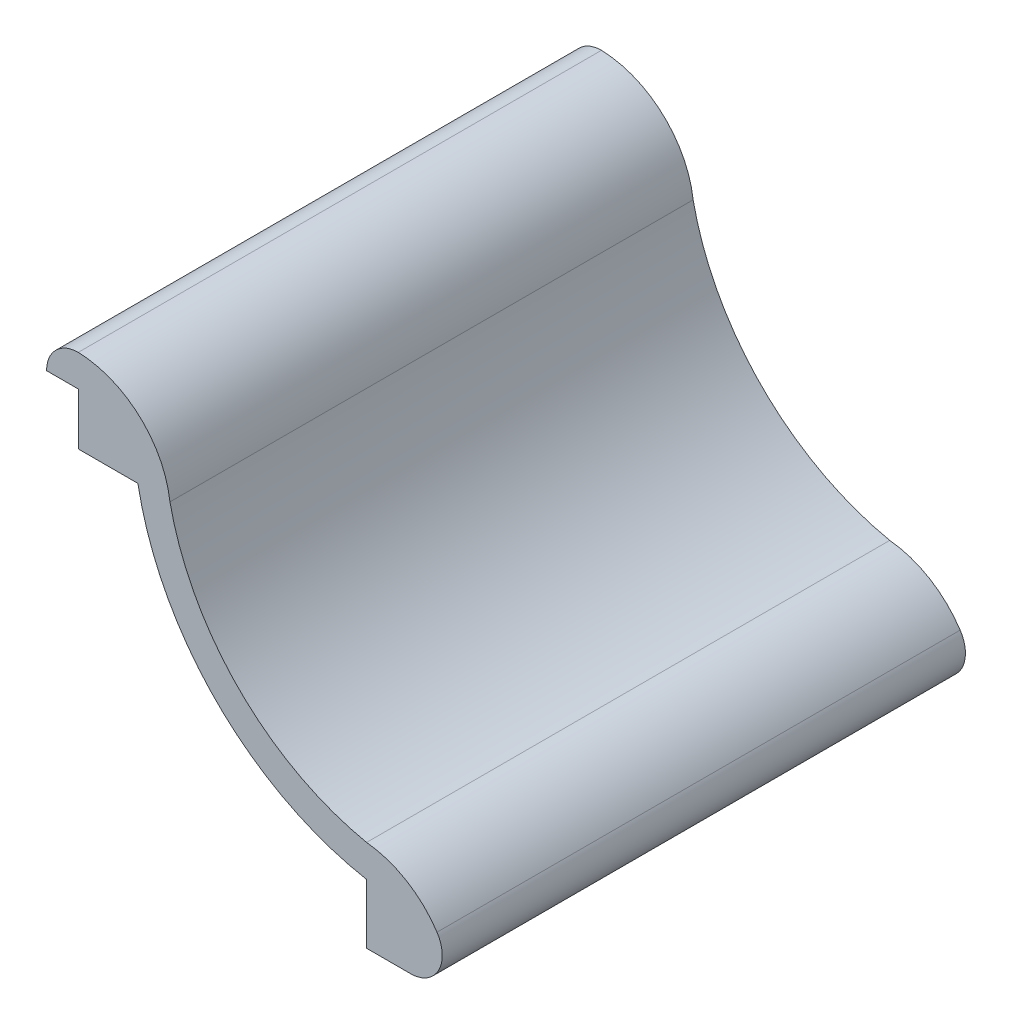
SolidWorks part; units mm, degrees
ref_plane "Front Plane" through (0, 0, 0) normal (0, 0, 1) x (1, 0, 0)
ref_plane "Top Plane" through (0, 0, 0) normal (0, 1, 0) x (1, 0, 0)
ref_plane "Right Plane" through (0, 0, 0) normal (1, 0, 0) x (0, 0, -1)
sketch "Sketch1" plane through (0, 0, 0) normal (0, 0, 1) x (1, 0, 0)
  line L4 (-45.7962, 45.7962) -> (0, 45.7962) construction
  line L6 (0, 45.7962) -> (0, 0) construction
  line L7 (-58.2422, 56.2102) -> (-58.2422, 62.5602)
  line L8 (10.922, -12.446) -> (17.272, -12.446)
  line L9 (-58.2422, 56.2102) -> (-58.2422, 45.7962) construction
  line L10 (-58.2422, 45.7962) -> (-45.7962, 45.7962) construction
  line L11 (0, 0) -> (0, -12.446) construction
  line L12 (0, -12.446) -> (10.922, -12.446) construction
  arc A6 (0, 0) -> (-45.7962, 45.7962) centre (10.3996, 56.1958) cw
  arc A7 (-45.7962, 45.7962) -> (-58.2422, 56.2102) centre (-58.3145, 43.4796) ccw
  arc A8 (0, 0) -> (10.922, -12.446) centre (-1.8079, -12.6018) cw
  arc A9 (-58.2422, 62.5602) -> (-39.3749, 45.7962) centre (-58.3145, 43.4796) cw
  arc A10 (-39.3749, 45.7962) -> (0, 6.4213) centre (10.3996, 56.1958) ccw
  arc A11 (0, 6.4213) -> (17.272, -12.446) centre (-1.8793, -12.6385) cw
  dimension "D1" = 45.7962
  dimension "D2" = 57.15
  dimension "D3" = 10.414
  dimension "D5" = 12.446
  dimension "D4" = 6.35
  dimension "D6" = 12.446
  dimension "D7" = 10.922
extrude "Boss-Extrude1" add sketch "Sketch1" along normal mid plane 209.55 contours L4 | A11 L8 A8 A6 A7 L7 A9 A10 region at (-42.5855, 44.9377, 0)
sketch "Sketch2" plane through (0, 0, 0) normal (0, 0, 1) x (1, 0, 0)
  line L0 (-58.2422, 56.2102) -> (-58.2422, 45.7962)
  line L1 (-58.2422, 45.7962) -> (-45.7962, 45.7962)
  line L2 (0, 0) -> (0, -12.446)
  line L3 (0, -12.446) -> (10.922, -12.446)
  arc A0 (-45.7962, 45.7962) -> (-58.2422, 56.2102) centre (-58.3145, 43.4796) ccw construction
  arc A1 (-45.7962, 45.7962) -> (0, 0) centre (10.3996, 56.1958) ccw construction
  arc A2 (-58.2422, 56.2102) -> (-45.7962, 45.7962) centre (-58.3145, 43.4796) cw
  arc A3 (0, 0) -> (10.922, -12.446) centre (-1.8079, -12.6018) cw
extrude "Boss-Extrude2" add sketch "Sketch2" along normal mid plane 185.1914
sketch "Sketch3" plane through (0, 0, -104.775) normal (0, 0, -1) x (-1, 0, 0)
  line L0 (58.2422, 56.2102) -> (58.2422, 45.7962)
  line L1 (58.2422, 45.7962) -> (45.7962, 45.7962)
  line L2 (0, 0) -> (0, -12.446)
  line L3 (0, -12.446) -> (-10.922, -12.446)
  arc A0 (-10.922, -12.446) -> (0, 0) centre (1.8079, -12.6018) cw
  arc A1 (45.7962, 45.7962) -> (58.2422, 56.2102) centre (58.3145, 43.4796) cw
extrude "Boss-Extrude3" add sketch "Sketch3" against normal offset from surface (5.8293 mm away) 6.35 up to face at (-53.4687, 50.0142, -92.5957)
sketch "Sketch4" plane through (0, 0, 104.775) normal (0, 0, 1) x (1, 0, 0)
  line L0 (-58.2422, 56.2102) -> (-58.2422, 45.7962)
  line L1 (-58.2422, 45.7962) -> (-45.7962, 45.7962)
  line L2 (0, 0) -> (0, -12.446)
  line L3 (0, -12.446) -> (10.922, -12.446)
  arc A0 (-58.2422, 56.2102) -> (-45.7962, 45.7962) centre (-58.3145, 43.4796) cw
  arc A1 (0, 0) -> (10.922, -12.446) centre (-1.8079, -12.6018) cw
extrude "Boss-Extrude4" add sketch "Sketch4" against normal blind 6.35
sketch "Sketch5" plane through (0, 0, 104.775) normal (0, 0, 1) x (1, 0, 0)
  line L0 (-58.2422, 45.7962) -> (-58.2422, 62.5602) construction
  line L2 (-57.7342, 44.7636) -> (-65.5217, 44.7636)
  line L3 (-57.7342, 44.7636) -> (-57.7342, 64.5974)
  line L4 (-57.7342, 64.5974) -> (-65.5217, 64.5974)
  line L5 (-65.5217, 44.7636) -> (-65.5217, 64.5974)
  line L6 (-3.152, -11.938) -> (19.6021, -11.938)
  line L7 (-3.152, -11.938) -> (-3.152, -15.345)
  line L8 (-3.152, -15.345) -> (19.6021, -15.345)
  line L9 (19.6021, -11.938) -> (19.6021, -15.345)
  line L10 (0, -12.446) -> (17.272, -12.446) construction
  dimension "D1" = 0.508
  dimension "D2" = 0.508
extrude "Cut-Extrude1" cut sketch "Sketch5" against normal through all
ref_plane "Plane1" [suppressed] through (-5.969, -5.969, 0) normal (-0.7071, -0.7071, 0) x (-0.7071, 0.7071, 0)
sketch "Sketch6" [suppressed] plane through (-5.969, -5.969, 0) normal (-0.7071, -0.7071, 0) x (-0.7071, 0.7071, 0)
  line L0 (0, 75.9801) -> (64.7656, 75.9801) construction
  line L1 (0, -92.5957) -> (0, 92.5957) construction
  line L2 (64.7656, -92.5957) -> (64.7656, 92.5957) construction
  circle A0 centre (32.3828, 75.9801) radius 6.35
  point P9 (32.3828, 75.9801)
  dimension "D1" = 12.7
extrude "Cut-Extrude2" [suppressed] cut sketch "Sketch6" against normal mid plane 12.7
sketch "Sketch7" plane through (0, 0, 104.775) normal (0, 0, 1) x (1, 0, 0)
  line L5 (-67.6333, 74.6841) -> (21.8261, 74.6841)
  line L6 (-67.6333, 74.6841) -> (-67.6333, -18.424)
  line L7 (-67.6333, -18.424) -> (21.8261, -18.424)
  line L8 (21.8261, 74.6841) -> (21.8261, -18.424)
extrude "Cut-Extrude3" [suppressed] cut sketch "Sketch7" against normal blind 104.775
sketch "Sketch8" [suppressed] plane through (-57.7342, 0, 0) normal (-1, 0, 0) x (0, 0, 1)
  line L0 (0, 62.5515) -> (0, 45.7962) construction
  line L1 (-104.775, 62.5515) -> (0, 62.5515)
  line L2 (-104.775, 62.5515) -> (-104.775, 56.1972)
  line L3 (-104.775, 56.1972) -> (0, 56.1972)
  line L4 (0, 62.5515) -> (0, 56.1972)
  line L5 (-98.9457, 56.1972) -> (-92.5957, 56.1972) construction
extrude "Boss-Extrude5" [suppressed] add sketch "Sketch8" along normal blind 6.35
fillet "Fillet1" [suppressed] radius 6.35
sketch "Sketch9" plane through (0, 0, -104.775) normal (0, 0, -1) x (-1, 0, 0)
  line L5 (-35.3187, 79.8232) -> (68.4231, 79.8232)
  line L6 (-35.3187, 79.8232) -> (-35.3187, -26.7531)
  line L7 (-35.3187, -26.7531) -> (68.4231, -26.7531)
  line L8 (68.4231, 79.8232) -> (68.4231, -26.7531)
extrude "Cut-Extrude4" cut sketch "Sketch9" against normal blind 104.775
sketch "Sketch10" plane through (-57.7342, 0, 0) normal (-1, 0, 0) x (0, 0, 1)
  line L0 (104.775, 45.7962) -> (104.775, 62.5515) construction
  line L1 (0, 62.5515) -> (104.775, 62.5515)
  line L2 (0, 62.5515) -> (0, 56.1972)
  line L3 (0, 56.1972) -> (104.775, 56.1972)
  line L4 (104.775, 62.5515) -> (104.775, 56.1972)
  line L5 (92.5957, 56.1972) -> (98.425, 56.1972) construction
extrude "Boss-Extrude6" add sketch "Sketch10" along normal blind 6.35
fillet "Fillet2" radius 6.35 2 edges at (17.2602, -11.938, 52.3875) (-64.0842, 62.5515, 52.3875)
